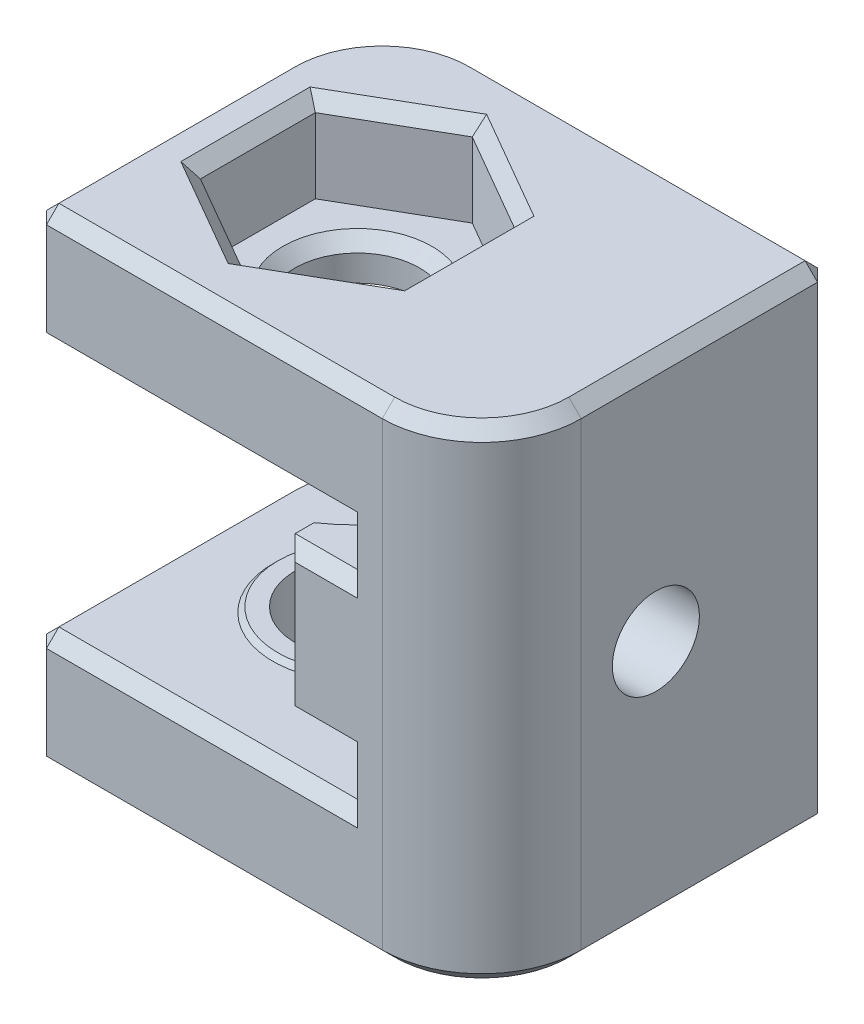
SolidWorks part; units mm, degrees
ref_plane "Front Plane" through (0, 0, 0) normal (0, 0, 1) x (1, 0, 0)
ref_plane "Top Plane" through (0, 0, 0) normal (0, 1, 0) x (1, 0, 0)
ref_plane "Right Plane" through (0, 0, 0) normal (1, 0, 0) x (0, 0, -1)
sketch "Sketch1" plane through (0, 0, 0) normal (0, 0, 1) x (1, 0, 0)
  line L0 (0, -9.75) -> (18, -9.75)
  line L1 (18, -9.75) -> (18, 9.75)
  line L2 (18, 9.75) -> (0, 9.75)
  line L3 (0, 9.75) -> (0, 5)
  line L4 (0, 5) -> (13, 5)
  line L5 (13, 5) -> (13, -5)
  line L6 (13, -5) -> (0, -5)
  line L7 (0, -5) -> (0, -9.75)
  line L8 (13, 0) -> (-2.5992, 0) construction
  dimension "D1" = 10
  dimension "D2" = 19.5
  dimension "D3" = 13
  dimension "D4" = 5
extrude "Boss-Extrude1" add sketch "Sketch1" along normal blind 14
sketch "Sketch2" plane through (0, 9.75, 0) normal (0, 1, 0) x (1, 0, 0)
  line L0 (0, -7) -> (18, -7) construction
  line L1 (0, -14) -> (0, 0) construction
  line L2 (18, -14) -> (18, 0) construction
  circle A0 centre (6, -7) radius 2.5
  dimension "D1" = 5
  dimension "D2" = 6
extrude "Cut-Extrude1" cut sketch "Sketch2" against normal through all
sketch "Sketch3" plane through (0, -5, 0) normal (0, 1, 0) x (1, 0, 0)
  circle A0 centre (6, -7) radius 9.5
  dimension "D1" = 19
extrude "Cut-Extrude2" cut sketch "Sketch3" along normal blind 2
extrude "Cut-Extrude3" cut sketch "Sketch3<2>" against normal blind 2 from surface starting at face at (6, 5, 9.5)
sketch "Sketch3<2>" plane through (0, -5, 0) normal (0, 1, 0) x (1, 0, 0) same geometry as "Sketch3"
sketch "Sketch4" plane through (0, 0, 0) normal (0, 1, 0) x (1, 0, 0)
  line L0 (10, -14) -> (13.7223, -14)
  line L1 (18, -14) -> (0, -14) construction
  line L2 (13.7223, -14) -> (13.7223, 0)
  line L3 (18, 0) -> (0, 0) construction
  line L4 (13.7223, 0) -> (10, 0)
  line L5 (10, 0) -> (10, -1.2554)
  line L6 (10, -12.7446) -> (10, -14)
  arc A0 (10, -12.7446) -> (10, -1.2554) centre (6, -7) ccw
  dimension "D1" = 14
  dimension "D2" = 3
extrude "Boss-Extrude2" add sketch "Sketch4" along normal up to surface and the other way up to surface up to face at (14.25, 3, 7) other way up to face at (14.25, -3, 7)
sketch "Sketch5" plane through (18, 0, 0) normal (1, 0, 0) x (0, 0, -1)
  line L0 (0, 0) -> (-14, 0) construction
  line L1 (-14, -9.75) -> (-14, 9.75) construction
  circle A0 centre (-7, 0) radius 1.75
  dimension "D1" = 3.5
extrude "Cut-Extrude4" cut sketch "Sketch5" against normal blind 3.6
sketch "Sketch6" plane through (0, 9.75, 0) normal (0, 1, 0) x (1, 0, 0)
  line L1 (6, -2.3812) -> (2, -4.6906)
  line L2 (2, -4.6906) -> (2, -9.3094)
  line L3 (2, -9.3094) -> (6, -11.6188)
  line L4 (6, -11.6188) -> (10, -9.3094)
  line L5 (10, -9.3094) -> (10, -4.6906)
  line L6 (10, -4.6906) -> (6, -2.3812)
  circle A0 centre (6, -7) radius 4 construction
  dimension "D1" = 8
extrude "Cut-Extrude5" cut sketch "Sketch6" against normal blind 3.5
sketch "Sketch7" plane through (0, -9.75, 0) normal (0, -1, 0) x (1, 0, 0)
  circle A0 centre (6, 7) radius 4.9
  dimension "D1" = 9.8
extrude "Cut-Extrude6" cut sketch "Sketch7" against normal blind 1
sketch "Sketch9" plane through (0, 5, 0) normal (0, -1, 0) x (1, 0, 0)
  circle A0 centre (6, 7) radius 2.5 construction
  circle A1 centre (6, 7) radius 2.5
  circle A2 centre (6, 7) radius 3.5
  dimension "D1" = 7
extrude "Boss-Extrude3" add sketch "Sketch9" along normal blind 0.3
extrude "Boss-Extrude5" add sketch "Sketch9<2>" against normal blind 0.2 from surface starting at face at (9.0833, -5, 7)
sketch "Sketch9<2>" plane through (0, 5, 0) normal (0, -1, 0) x (1, 0, 0) same geometry as "Sketch9"
fillet "Fillet1" radius 4 3 edges at (18, 0, 14) (0, -7.375, 0) (0, 7.375, 0)
chamfer "Chamfer1" distance 0.5 angle 45 7 edges at (4, 9.75, 10.4641) (2, 9.75, 7) (4, 9.75, 3.5359) (8, 9.75, 3.5359) (8, 9.75, 10.4641) (10, 9.75, 7) (6, -9.75, 2.1)
chamfer "Chamfer2" distance 0.3 angle 45 2 edges at (9.5, 4.7, 7) (9.5, -4.8, 7)
chamfer "Chamfer3" distance 0.5 angle 45 31 edges at (11.5, 3, 0) (11.5, -3, 0) (10, 0, 0) (11.5, -3, 14) (11.5, 3, 14) (10, 0, 14) (6, -8.75, 4.5) (3.5, 6.25, 7) (0, -9.75, 9) (1.1716, -9.75, 1.1716) (18, 0, 0) (11, -9.75, 0) (8.5, -5, 0) (18, -9.75, 5) (1.1716, -5, 1.1716) (16.8284, -9.75, 12.8284) (0, -5, 9) (6.5, -5, 14) (0, -7.375, 14) (7, -9.75, 14) (11, 9.75, 0) (8.5, 5, 0) (18, 9.75, 5) (1.1716, 9.75, 1.1716) (1.1716, 5, 1.1716) (16.8284, 9.75, 12.8284) (0, 9.75, 9) (0, 5, 9) (7, 9.75, 14) (6.5, 5, 14) (0, 7.375, 14)
